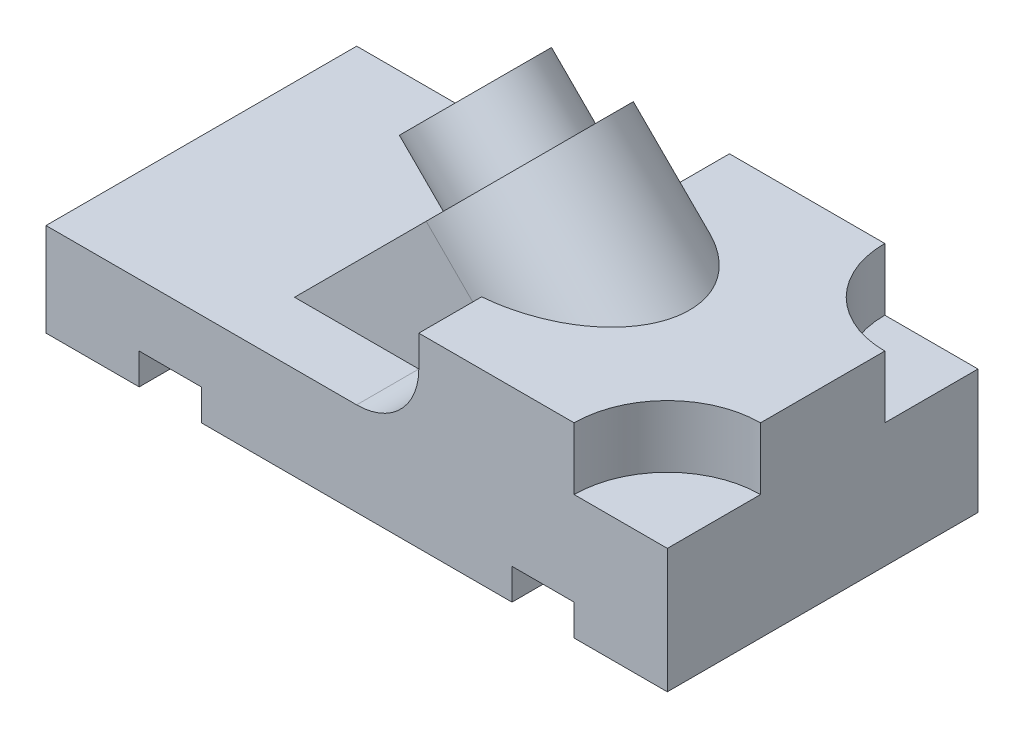
SolidWorks part; units mm, degrees
material "Ductile Iron"
ref_plane "Front Plane" through (0, 0, 0) normal (0, 0, 1) x (1, 0, 0)
ref_plane "Top Plane" through (0, 0, 0) normal (0, 1, 0) x (1, 0, 0)
ref_plane "Right Plane" through (0, 0, 0) normal (1, 0, 0) x (0, 0, -1)
sketch "Sketch1" plane through (0, 0, 0) normal (0, 0, 1) x (1, 0, 0)
  line L0 (0, 0) -> (0, 15)
  line L1 (0, 15) -> (50, 15)
  line L2 (60, 25) -> (60, 30)
  line L3 (60, 30) -> (100, 30)
  line L4 (100, 30) -> (100, 0)
  line L5 (100, 0) -> (0, 0)
  arc A0 (50, 15) -> (60, 25) centre (50, 25) ccw
  dimension "D5" = 10
  dimension "D1" = 100
  dimension "D2" = 30
  dimension "D3" = 40
  dimension "D4" = 15
extrude "Boss-Extrude1" add sketch "Sketch1" along normal blind 50
ref_plane "Plane1" through (30, 0, 0) normal (-1, 0, 0) x (0, 0, 1)
ref_axis "Axis1" through (30, 15, 0) along (0, 0, 1)
ref_plane "Plane2" through (7.5, -7.5, 0) normal (-0.7071, 0.7071, 0) x (0, 0, 1)
sketch "Sketch2" plane through (7.5, -7.5, 0) normal (-0.7071, 0.7071, 0) x (0, 0, 1)
  line L0 (10, 31.7832) -> (40, 31.7832)
  line L1 (40, 31.7832) -> (40, 61.7832)
  line L2 (10, 31.7832) -> (10, 61.7832)
  line L3 (40, 31.7832) -> (50, 31.7832)
  line L4 (0, 45.9619) -> (0, 10.6066)
  line L5 (0, 10.6066) -> (50, 10.6066)
  line L6 (50, 10.6066) -> (50, 45.9619)
  line L7 (50, 45.9619) -> (0, 45.9619)
  line L8 (0, 45.9619) -> (0, 10.6066)
  line L9 (0, 10.6066) -> (50, 10.6066)
  line L10 (50, 10.6066) -> (50, 45.9619)
  line L11 (50, 45.9619) -> (0, 45.9619)
  arc A0 (10, 61.7832) -> (40, 61.7832) centre (25, 61.7832) cw
  dimension "D2" = 30
  dimension "D3" = 10
  dimension "D4" = 30
  dimension "D1" = 0
extrude "Boss-Extrude2" add sketch "Sketch2" against normal up to next contours L1 L11 L2 L0 | A0 L2 L11 L1 region at (34.987, 19.987, 25) region at (49.9024, 34.9024, 25)
sketch "Sketch3" plane through (7.5, -7.5, 0) normal (-0.7071, 0.7071, 0) x (0, 0, 1)
  circle A0 centre (25, 61.7832) radius 10
  circle A1 centre (25, 61.7832) radius 5
  dimension "D1" = 20
  dimension "D2" = 10
extrude "Boss-Extrude3" add sketch "Sketch3" along normal blind 10
sketch "Sketch4" plane through (0, 30, 0) normal (0, 1, 0) x (1, 0, 0)
  circle A0 centre (100, 0) radius 15
  circle A1 centre (100, -50) radius 15
  dimension "D1" = 30
  dimension "D2" = 30
extrude "Cut-Extrude1" cut sketch "Sketch4" against normal blind 10
sketch "Sketch5" plane through (0, 0, 50) normal (0, 0, 1) x (1, 0, 0)
  line L0 (0, 0) -> (15, 0)
  line L1 (0, 0) -> (100, 0) construction
  line L2 (15, 0) -> (15, 5)
  line L3 (15, 5) -> (25, 5)
  line L4 (25, 5) -> (25, 0)
  line L5 (25, 0) -> (15, 0)
  line L6 (25, 0) -> (75, 0)
  line L7 (75, 0) -> (75, 5)
  line L8 (75, 5) -> (85, 5)
  line L9 (85, 5) -> (85, 0)
  line L10 (85, 0) -> (75, 0)
  line M14 (0, 0) -> (100, 0)
  dimension "D1" = 50
  dimension "D2" = 15
  dimension "D3" = 10
  dimension "D4" = 5
  dimension "D5" = 5
  dimension "D6" = 10
extrude "Cut-Extrude2" cut sketch "Sketch5" against normal through all contours L4 L3 L2 M14 | L9 L8 L7 M14 region at (80, 2.5, 50) region at (20, 2.5, 50)
